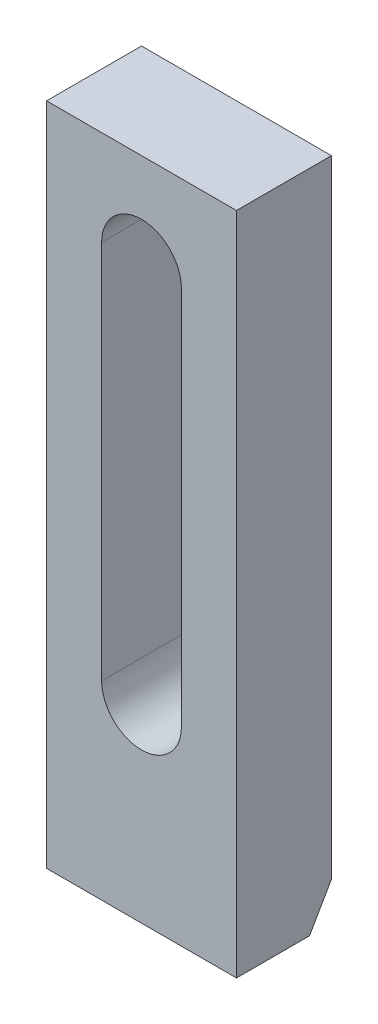
SolidWorks part; units mm, degrees
material "Простая углеродистая сталь"
ref_plane "Спереди" through (0, 0, 0) normal (0, 0, 1) x (1, 0, 0)
ref_plane "Сверху" through (0, 0, 0) normal (0, 1, 0) x (1, 0, 0)
ref_plane "Справа" through (0, 0, 0) normal (1, 0, 0) x (0, 0, -1)
sketch "Эскиз1" plane through (0, 0, 0) normal (0, 0, 1) x (1, 0, 0)
  line L1 (0, 0) -> (50, 0)
  line L2 (0, 0) -> (0, 175)
  line L3 (0, 175) -> (50, 175)
  line L4 (50, 0) -> (50, 175)
  dimension "D1" = 50
  dimension "D2" = 175
extrude "Бобышка-Вытянуть1" add sketch "Эскиз1" along normal blind 25
sketch "Эскиз2" plane through (0, 0, 25) normal (0, 0, 1) x (1, 0, 0)
  line L1 (14.5, 50) -> (14.5, 150)
  line L2 (35.5, 50) -> (35.5, 150)
  line L3 (0, 175) -> (0, 0) construction
  line L4 (0, 0) -> (50, 0) construction
  arc A0 (14.5, 50) -> (35.5, 50) centre (25, 50) ccw
  arc A1 (14.5, 150) -> (35.5, 150) centre (25, 150) cw
  point P7 (14.5, 100)
  point P10 (35.5, 100)
  dimension "D1" = 25
  dimension "D2" = 50
extrude "Вырез-Вытянуть1" cut sketch "Эскиз2" against normal through all
chamfer "Фаска1" distance 10 angle 30 1 edges at (25, 0, 0) first distance on face at (25, 100, 0)
